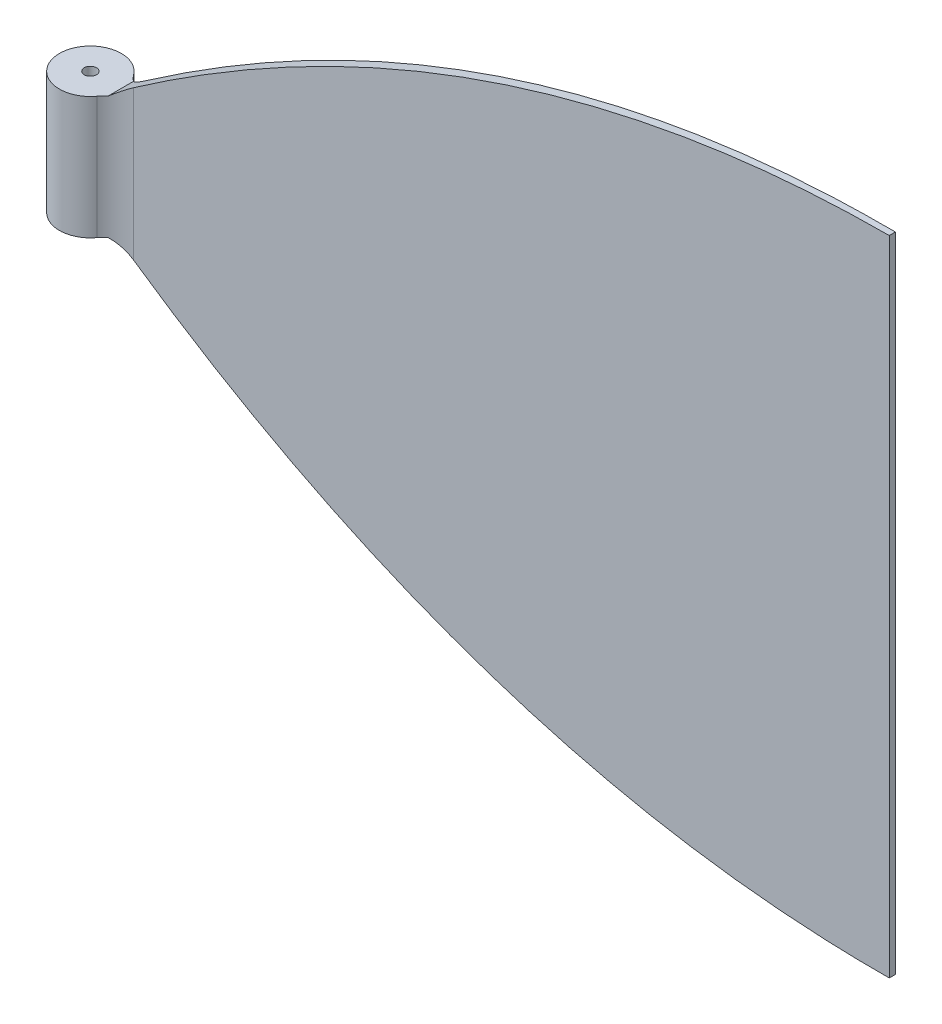
SolidWorks part; units mm, degrees
ref_plane "Спереди" through (0, 0, 0) normal (0, 0, 1) x (1, 0, 0)
ref_plane "Сверху" through (0, 0, 0) normal (0, 1, 0) x (1, 0, 0)
ref_plane "Справа" through (0, 0, 0) normal (1, 0, 0) x (0, 0, -1)
sketch "Эскиз1" plane through (0, 0, 0) normal (0, 0, 1) x (1, 0, 0)
  line L0 (0, 0) -> (0, 57429.9207) construction
  line L1 (20, -12.462) -> (20, 57417.4587) construction
  line L2 (270, -31.3902) -> (270, 49968.6098) construction
  line L3 (0, 0) -> (50000, 0) construction
  line L4 (129.4653, 105) -> (50129.4653, 105) construction
  line L5 (119.2642, -105) -> (50119.2642, -105) construction
  line L6 (59.6461, 20) -> (-49940.3539, 20) construction
  line L7 (91.4751, -20) -> (-49908.5249, -20) construction
  line L8 (272, -72.6603) -> (272, 49927.3397) construction
  line L9 (272, -105) -> (272, 105)
  line L10 (20, 20) -> (20, -20)
  spline S0 degree 2 poles (20, -20) (138.9193, -105.3219) (272, -105) knots 0 0 0 1 1 1
  spline S1 degree 2 poles (20, 20) (138.9193, 105.3219) (272, 105) knots 0 0 0 1 1 1
  dimension "D1" = 20
  dimension "D2" = 250
  dimension "D3" = 105
  dimension "D4" = 105
  dimension "D5" = 20
  dimension "D6" = 20
  dimension "D7" = 2
extrude "Бобышка-Вытянуть1" add sketch "Эскиз1" along normal blind 2 and the other way blind 2
sketch "Эскиз2" plane through (0, 0, 0) normal (0, 1, 0) x (1, 0, 0)
  line L0 (272, 2) -> (272, -2) construction
  line L1 (20, -2) -> (272, -1)
  line L2 (272, 1) -> (20, 2)
  line L3 (272, 1) -> (272, 2)
  line L4 (272, 2) -> (20, 2)
  line L5 (20, -2) -> (272, -2)
  line L6 (272, -2) -> (272, -1)
  point P2 (272, 0)
  dimension "D1" = 1
  dimension "D2" = 1
extrude "Вырез-Вытянуть1" cut sketch "Эскиз2" against normal through all and the other way through all
sketch "Эскиз4" plane through (0, 0, 0) normal (0, 1, 0) x (1, 0, 0)
  line L0 (20, 2) -> (-49980, 2) construction
  line L1 (20, -2) -> (-49980, -2) construction
  line L2 (0, 0) -> (0, 50000) construction
  line L3 (20, 0.7676) -> (20, -49999.2324) construction
  line L5 (20, 2) -> (20, -2)
  arc A0 (20, 2) -> (20, -2) centre (10.1, 0) ccw
extrude "Бобышка-Вытянуть2" add sketch "Эскиз4" along normal up to vertex (20 mm away) and the other way up to vertex (20 mm away) up to point (20, 20, -2) other way up to point (20, -20, -2)
fillet "Скругление1" radius 10 2 edges at (20, 0, -2) (20, 0, 2)
sketch "Эскиз5" plane through (0, 20, 0) normal (0, 1, 0) x (1, 0, 0)
  circle A0 centre (10.1, 0) radius 2
extrude "Вырез-Вытянуть2" cut sketch "Эскиз5" against normal up to surface (40 mm away) up to face at (14.523, -20, 0)
